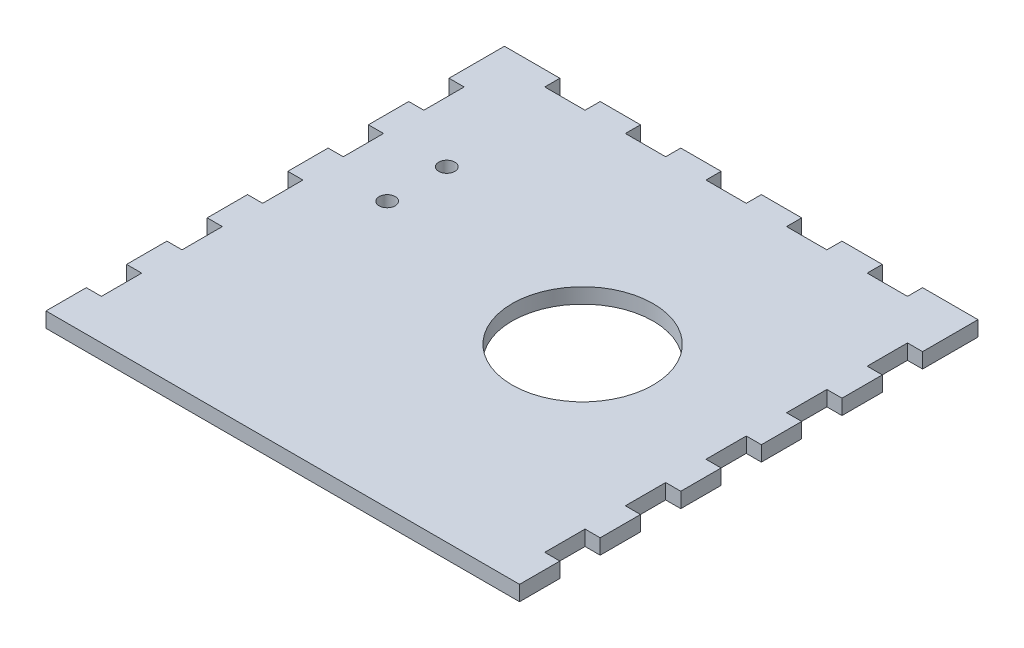
SolidWorks part; units mm, degrees
ref_plane "Front Plane" through (0, 0, 0) normal (0, 0, 1) x (1, 0, 0)
ref_plane "Top Plane" through (0, 0, 0) normal (0, 1, 0) x (1, 0, 0)
ref_plane "Right Plane" through (0, 0, 0) normal (1, 0, 0) x (0, 0, -1)
sketch "Sketch1" plane through (0, 0, 0) normal (0, 1, 0) x (1, 0, 0)
  line L1 (-139.7, -139.7) -> (139.7, -139.7)
  line L2 (-139.7, -139.7) -> (-139.7, 139.7)
  line L3 (-139.7, 139.7) -> (139.7, 139.7)
  line L4 (139.7, -139.7) -> (139.7, 139.7)
  line L5 (-139.7, -139.7) -> (139.7, 139.7) construction
  line L6 (-139.7, 139.7) -> (139.7, -139.7) construction
  point P0 (0, 0)
  dimension "D1" = 279.4
  dimension "D2" = 279.4
extrude "Boss-Extrude1" add sketch "Sketch1" along normal blind 9.525
sketch "Sketch2" plane through (139.7, 0, 0) normal (1, 0, 0) x (0, 0, -1)
  line L0 (-139.7, 9.525) -> (139.7, 9.525) construction
  line L1 (-139.7, 0) -> (-114.3, 0)
  line L2 (-139.7, 0) -> (-139.7, 9.525)
  line L3 (-139.7, 9.525) -> (-114.3, 9.525)
  line L4 (-114.3, 0) -> (-114.3, 9.525)
  dimension "D1" = 25.4
extrude "Boss-Extrude2" add sketch "Sketch2" along normal blind 9.525
pattern_linear "LPattern1" count 6 spacing 50.8 along (0, 0, -1) of "Boss-Extrude2"
mirror "Mirror1" about plane through (0, 0, 0) normal (1, 0, 0) of "LPattern1"
sketch "Sketch3" plane through (0, 0, -139.7) normal (0, 0, -1) x (-1, 0, 0)
  line L0 (-149.225, 9.525) -> (149.225, 9.525) construction
  line L1 (-139.7, 9.525) -> (-114.3, 9.525)
  line L2 (-139.7, 9.525) -> (-139.7, 0)
  line L3 (-139.7, 0) -> (-114.3, 0)
  line L4 (-114.3, 9.525) -> (-114.3, 0)
  line L5 (-149.225, 0) -> (149.225, 0) construction
  line L6 (-149.225, 0) -> (-149.225, 9.525) construction
  dimension "D1" = 9.525
  dimension "D2" = 25.4
extrude "Boss-Extrude3" add sketch "Sketch3" along normal blind 9.525
pattern_linear "LPattern2" count 6 spacing 50.8 along (-1, 0, 0) of "Boss-Extrude3"
sketch "Sketch5" plane through (0, 0, -139.7) normal (0, 0, -1) x (-1, 0, 0)
  line L0 (158.9088, 0) -> (-158.9088, 0) construction
  line L1 (-149.225, 9.525) -> (-139.7, 9.525)
  line L2 (-149.225, 9.525) -> (-149.225, 0)
  line L3 (-149.225, 0) -> (-139.7, 0)
  line L4 (-139.7, 9.525) -> (-139.7, 0)
  line L5 (-139.7, 9.525) -> (-139.7, 0) construction
extrude "Boss-Extrude4" add sketch "Sketch5" along normal blind 9.525
mirror "Mirror2" about plane through (0, 0, 0) normal (1, 0, 0) of "Boss-Extrude4"
sketch "Sketch6" plane through (0, 9.525, 0) normal (0, 1, 0) x (1, 0, 0)
  line L0 (63.5, 139.7) -> (38.1, 139.7) construction
  line L1 (139.7, -12.7) -> (139.7, 12.7) construction
  circle A0 centre (38.1, 11.176) radius 44.45
  dimension "D1" = 128.524
  dimension "D2" = 101.6
extrude "Cut-Extrude1" cut sketch "Sketch6" against normal through all
sketch "Sketch7" plane through (0, 9.525, 0) normal (0, 1, 0) x (1, 0, 0)
  line L0 (-139.7, 63.5) -> (-139.7, 38.1) construction
  line L1 (-139.7, 114.3) -> (-139.7, 88.9) construction
  line L2 (-88.9, 139.7) -> (-114.3, 139.7) construction
  circle A0 centre (-101.6, 65.278) radius 5.08
  circle A1 centre (-101.6, 27.686) radius 5.08
  dimension "D1" = 10.16
  dimension "D2" = 10.16
  dimension "D3" = 38.1
  dimension "D4" = 38.1
  dimension "D5" = 37.592
  dimension "D6" = 74.422
extrude "Cut-Extrude2" cut sketch "Sketch7" against normal through all
sketch "Sketch9" plane through (0, 9.525, 0) normal (0, 1, 0) x (1, 0, 0)
  circle A0 centre (-101.6, 65.2827) radius 11 construction
  circle A1 centre (-101.6, 27.6073) radius 25.4
  circle A2 centre (-101.6, 27.6073) radius 25.4
  circle A3 centre (-101.6, 65.2827) radius 11
  dimension "D1" = 0
